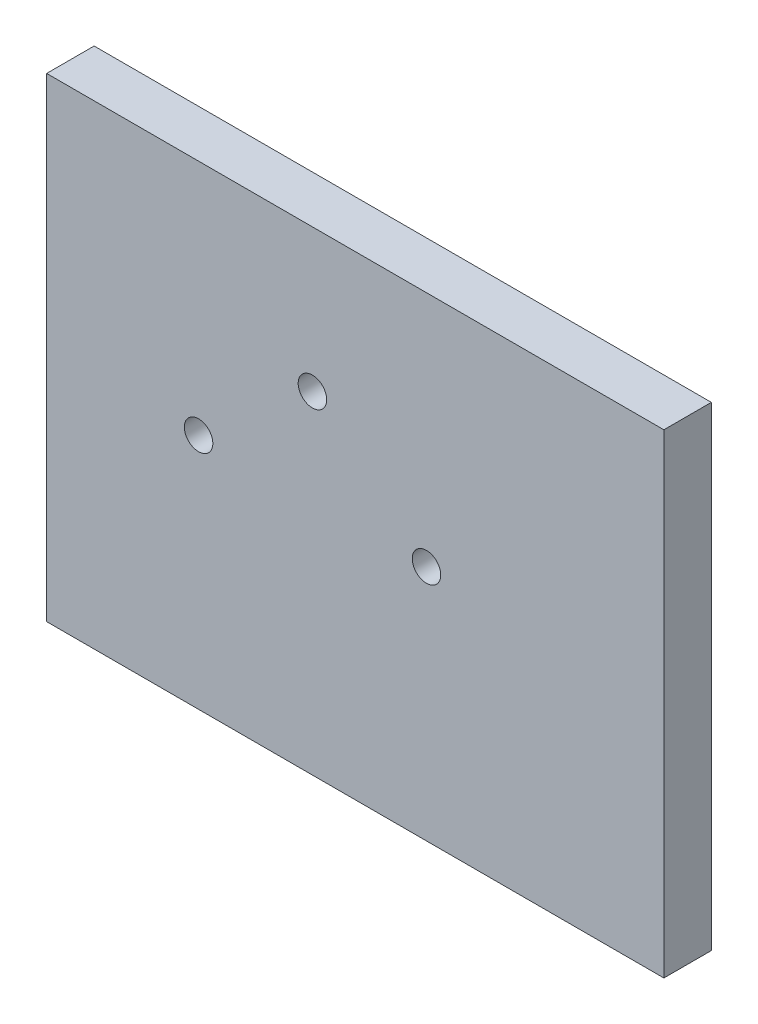
SolidWorks part; units mm, degrees
ref_plane "Front Plane" through (0, 0, 0) normal (0, 0, 1) x (1, 0, 0)
ref_plane "Top Plane" through (0, 0, 0) normal (0, 1, 0) x (1, 0, 0)
ref_plane "Right Plane" through (0, 0, 0) normal (1, 0, 0) x (0, 0, -1)
sketch "Sketch3" plane through (0, 0, 0) normal (0, 0, 1) x (1, 0, 0)
  line L1 (0, 0) -> (65, 0)
  line L2 (0, 0) -> (0, -50)
  line L3 (0, -50) -> (65, -50)
  line L4 (65, 0) -> (65, -50)
  dimension "D1" = 65
  dimension "D2" = 50
extrude "Boss-Extrude2" add sketch "Sketch3" along normal blind 5
sketch "Sketch4" plane through (0, 0, 5) normal (0, 0, 1) x (1, 0, 0)
  line L0 (65, -50) -> (65, 0) construction
  circle A0 centre (40, -25) radius 1.5
  circle A1 centre (16, -25) radius 1.5
  circle A2 centre (27.987, -15.0164) radius 1.5
  point P10 (38.1863, -21.1955)
  dimension "D2" = 3
  dimension "D3" = 3
  dimension "D5" = 3
  dimension "D1" = 25
  dimension "D4" = 24
  dimension "D6" = 15.6
  dimension "D7" = 15.62
extrude "Cut-Extrude2" cut sketch "Sketch4" against normal blind 5
